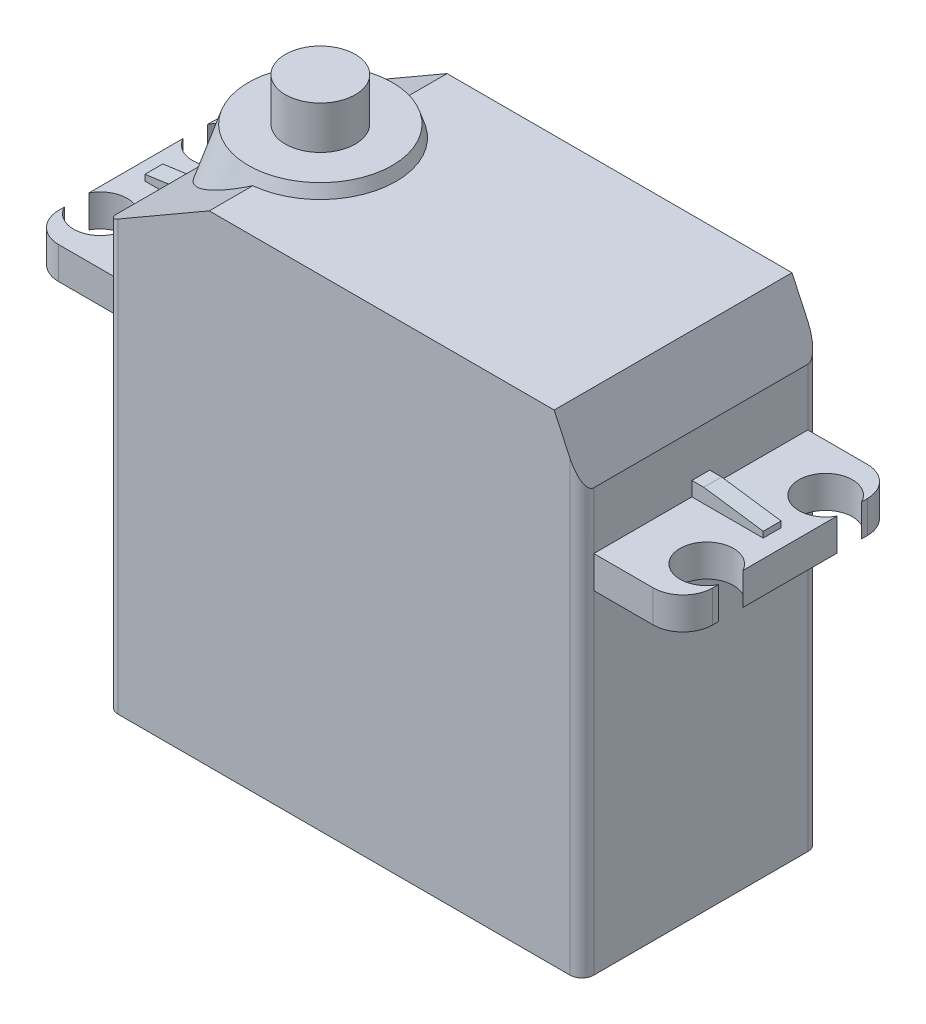
SolidWorks part; units mm, degrees
material "Caucho natural"
ref_plane "Alzado" through (0, 0, 0) normal (0, 0, 1) x (1, 0, 0)
ref_plane "Planta" through (0, 0, 0) normal (0, 1, 0) x (1, 0, 0)
ref_plane "Vista lateral" through (0, 0, 0) normal (1, 0, 0) x (0, 0, -1)
sketch "Croquis1" plane through (0, 0, 0) normal (0, 0, 1) x (1, 0, 0)
  line L5 (40, 0) -> (0, 0)
  line L6 (0, 0) -> (0, 35.5)
  line L7 (0, 35.5) -> (8.6588, 40.4992)
  line L8 (8.6588, 40.4992) -> (37.6688, 40.4992)
  line L9 (37.6688, 40.4992) -> (40, 35.5)
  line L10 (40, 35.5) -> (40, 0)
  line L11 (40, 35.5) -> (33.0118, 35.5) construction
  line L12 (0, 35.5) -> (9.1646, 35.5) construction
  dimension "D1" = 40
  dimension "D2" = 29.01
  dimension "D3" = 35.5
  dimension "D4" = 9.1646
  dimension "D5" = 35.5
  dimension "D6" = 6.9882
  dimension "D7" = 30
  dimension "D8" = 65
extrude "Saliente-Extruir1" add sketch "Croquis1" along normal blind 20
fillet "Redondeo1" radius 1 4 edges at (0, 17.75, 0) (0, 17.75, 20) (40, 17.75, 0) (40, 17.75, 20)
ref_plane "Plano1" through (0, 35.5, 0) normal (0, -1, 0) x (-1, 0, 0)
sketch "Croquis2" plane through (0, 35.5, 0) normal (0, -1, 0) x (-1, 0, 0)
  line L0 (0, -19) -> (0, -1) construction
  circle A0 centre (-8, -10) radius 8
  point P7 (0, -10)
  dimension "D1" = 16
extrude "Saliente-Extruir2" add sketch "Croquis2" against normal blind 6 draft 18
sketch "Croquis3" plane through (0, 41.5, 0) normal (0, 1, 0) x (1, 0, 0)
  circle A0 centre (8, -10) radius 2.94
  circle A1 centre (8, -10) radius 6.0505 construction
  dimension "D1" = 5.88
extrude "Saliente-Extruir3" add sketch "Croquis3" along normal blind 3.6
ref_plane "Plano2" through (0, 28.01, 0) normal (0, -1, 0) x (-1, 0, 0)
sketch "Croquis4" plane through (0, 28.01, 0) normal (0, -1, 0) x (-1, 0, 0)
  line L0 (0, -19) -> (0, -1) construction
  line L1 (-40, -19) -> (-45, -19)
  line L2 (-40, -19) -> (-40, -1)
  line L3 (-40, -1) -> (-45, -1)
  line L4 (-47.5, -16.5) -> (-47.5, -3.5)
  line L6 (-40, -19) -> (-40, -1) construction
  line L8 (5, -19) -> (0, -19)
  line L9 (7.5, -16.5) -> (7.5, -3.5)
  line L10 (5, -1) -> (0, -1)
  line L11 (0, -19) -> (0, -1)
  circle A0 centre (5.5, -15) radius 2.25
  circle A1 centre (5.5, -5) radius 2.25
  arc A2 (-45, -1) -> (-47.5, -3.5) centre (-45, -3.5) ccw
  arc A3 (-45, -19) -> (-47.5, -16.5) centre (-45, -16.5) cw
  arc A4 (7.5, -3.5) -> (5, -1) centre (5, -3.5) ccw
  arc A5 (5, -19) -> (7.5, -16.5) centre (5, -16.5) ccw
  circle A6 centre (-45.5, -15) radius 2.25
  circle A7 centre (-45.5, -5) radius 2.25
  dimension "D3" = 4.5
  dimension "D4" = 4.5
  dimension "D9" = 2.5
  dimension "D1" = 7.5
  dimension "D2" = 7.5
  dimension "D5" = 4
  dimension "D6" = 5.5
  dimension "D7" = 5.5
  dimension "D8" = 4
  dimension "D10" = 5.5
  dimension "D11" = 5.5
extrude "Saliente-Extruir4" add sketch "Croquis4" against normal blind 2.7 contours L8 A5 L9 A0 A1 A4 L10 L11 | A7 L4 A6 A3 L1 L2 L3 A2 region at (43.1418, 28.01, 10) region at (-3.1418, 28.01, 10)
ref_plane "Plano3" through (0, 0, 10) normal (0, 0, 1) x (1, 0, 0)
sketch "Croquis5" plane through (0, 0, 10) normal (0, 0, 1) x (1, 0, 0)
  line L0 (-6, 31.21) -> (-1.0002, 31.91)
  line L1 (-1.0002, 31.91) -> (0, 31.91)
  line L2 (0, 30.71) -> (0, 35.5) construction
  line L3 (-5, 30.71) -> (0, 30.71) construction
  line L4 (-6, 31.21) -> (-6, 30.71)
  line L5 (-6, 30.71) -> (0, 30.71)
  line L6 (0, 30.71) -> (0, 31.91)
  line L7 (-6, 31.21) -> (0, 31.21) construction
  line L8 (40, 31.91) -> (41.0002, 31.91)
  line L9 (40, 35.5) -> (40, 30.71) construction
  line L10 (41.0002, 31.91) -> (46, 31.21)
  line L11 (46, 31.21) -> (46, 30.71)
  line L12 (40, 30.71) -> (45, 30.71) construction
  line L13 (46, 30.71) -> (40, 30.71)
  line L14 (40, 30.71) -> (40, 31.91)
  line L15 (46, 31.21) -> (40, 31.21) construction
  dimension "D1" = 1.2
  dimension "D2" = 6
  dimension "D3" = 0.5
  dimension "D4" = 7.97
  dimension "D5" = 6
  dimension "D6" = 0.5
  dimension "D7" = 7.97
extrude "Saliente-Extruir5" add sketch "Croquis5" along normal mid plane 1.5
ref_axis "Eje1" through (8, 143.4599, 10) along (0, -1, 0)
